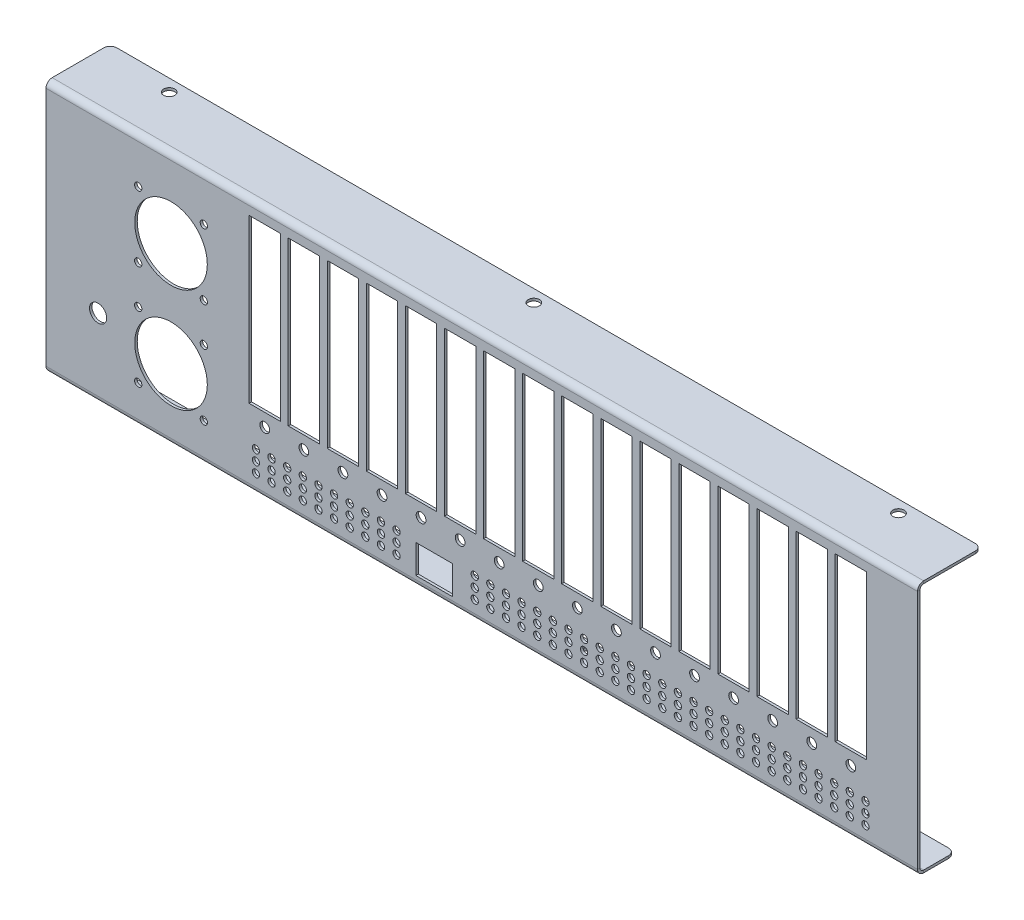
SolidWorks part; units mm, degrees
note: The reader was unsure of these and kept them because the rebuilt part matched: thickness of "Base-Flange", "Edge-Flange1", "Edge-Flange2".
ref_plane "Front" through (0, 0, 0) normal (0, 0, 1) x (1, 0, 0)
ref_plane "Top" through (0, 0, 0) normal (0, 1, 0) x (1, 0, 0)
ref_plane "Right" through (0, 0, 0) normal (1, 0, 0) x (0, 0, -1)
sketch "Sketch1" plane through (0, 0, 0) normal (0, 0, 1) x (1, 0, 0)
  line L1 (0, 0) -> (424.942, 0)
  line L2 (0, 0) -> (0, 123.3424)
  line L3 (0, 123.3424) -> (424.942, 123.3424)
  line L4 (424.942, 0) -> (424.942, 123.3424)
  dimension "Width" = 424.942
  dimension "Back Panel Height" = 123.3424
sheet metal parameters "Sheet-Metal1" thickness 1.2192 parameters "D1"=1.778
base flange "Base-Flange" sketch "Sketch1" thickness 1.2192 parameters "D1"=1.778
edge flange "Edge-Flange1" sketch "Sketch9" bend radius 1.778 thickness 1.2192 parameters "D6"=10
sketch "Sketch9" plane through (0, 123.3424, 0) normal (0, -1, 0) x (-1, 0, 0)
  line L1 (0, 0) -> (-424.942, 0) construction
  line L2 (-424.942, 0) -> (-424.942, 30.1498)
  line L3 (-424.942, 30.1498) -> (0, 30.1498)
  line L4 (0, 30.1498) -> (0, 0)
  line L5 (0, 0) -> (-424.942, 0)
bend "EdgeBend1" bend radius 1.778 bend angle 90 parameters "D5"=1
edge flange "Edge-Flange2" sketch "Sketch12" bend radius 1.778 thickness 1.2192 parameters "D6"=10
sketch "Sketch12" plane through (0, 0, 0) normal (0, 1, 0) x (1, 0, 0)
  line L1 (424.942, 0) -> (0, 0) construction
  line L2 (0, 0) -> (0, 17.145)
  line L3 (0, 17.145) -> (424.942, 17.145)
  line L4 (424.942, 17.145) -> (424.942, 0)
  line L5 (424.942, 0) -> (0, 0)
bend "EdgeBend2" bend radius 1.778 bend angle 90 parameters "D5"=2
sketch "Sketch13" plane through (0, 0, 0) normal (0, -1, 0) x (1, 0, 0)
  line L0 (0, 1.2192) -> (424.942, 1.2192) construction
  line L1 (250.571, -17.145) -> (250.571, 16.8625) construction
  circle A0 centre (34.671, -11.4808) radius 2.4765
  circle A1 centre (250.571, -11.4808) radius 2.4765
  circle A2 centre (390.271, -11.4808) radius 2.4765
  dimension "D1" = 4.953
  dimension "D2" = 12.7
  dimension "D3" = 215.9
  dimension "D4" = 139.7
extrude "8-32 Clearance For Chassi Studs" cut sketch "Sketch13" against normal blind 1.2192
sketch "Sketch14" plane through (0, 123.3424, 0) normal (0, 1, 0) x (-1, 0, 0)
  line L1 (-212.471, -1.778) -> (-212.471, -47.511) construction
  line L2 (-424.942, 1.2192) -> (0, 1.2192) construction
  line L4 (0, -1.778) -> (-424.942, -1.778) construction
  circle A0 centre (-390.271, -24.1808) radius 2.7051
  circle A1 centre (-212.471, -24.1808) radius 2.7051
  circle A2 centre (-34.671, -24.1808) radius 2.7051
  dimension "D1" = 5.4102
  dimension "D4" = 177.8
  dimension "D3" = 25.4
extrude "8-32 PEM Nuts For Cover Attachment" cut sketch "Sketch14" against normal blind 1.2192
fillet "Fillet1" radius 3.175 4 edges at (0, 122.7328, -30.1498) (424.942, 122.7328, -30.1498) (424.942, 0.6096, -17.145) (0, 0.6096, -17.145)
sketch "Sketch16" plane through (0, 0, 1.2192) normal (0, 0, 1) x (1, 0, 0)
  line L0 (424.942, 2.9972) -> (424.942, 120.3452) construction
  line L2 (424.942, 0) -> (0, 0) construction
  line L3 (384.81, 116.205) -> (400.05, 116.205)
  line L4 (384.81, 116.205) -> (384.81, 36.83)
  line L5 (384.81, 36.83) -> (400.05, 36.83)
  line L6 (400.05, 116.205) -> (400.05, 36.83)
  circle A0 centre (392.43, 30.48) radius 2.3813
  dimension "D1" = 4.7625
  dimension "D2" = 32.512
  dimension "D4" = 79.375
  dimension "D3" = 6.35
  dimension "D5" = 15.24
  dimension "D6" = 7.62
  dimension "D7" = 30.48
extrude "Cut-Extrude5" cut sketch "Sketch16" against normal blind 12.54
pattern_linear "LPattern1" count 16 spacing 19.05 along (-1, 0, 0) of "Cut-Extrude5"
sketch "Sketch17" plane through (0, 0, 1.2192) normal (0, 0, 1) x (1, 0, 0)
  line L0 (0, 120.3452) -> (0, 2.9972) construction
  line L1 (180.34, 18.7452) -> (198.12, 18.7452)
  line L2 (180.34, 18.7452) -> (180.34, 4.7752)
  line L3 (180.34, 4.7752) -> (198.12, 4.7752)
  line L4 (198.12, 18.7452) -> (198.12, 4.7752)
  line L5 (424.942, 1.2192) -> (0, 1.2192) construction
  dimension "D1" = 180.34
  dimension "D2" = 3.556
  dimension "D3" = 17.78
  dimension "D4" = 13.97
extrude "NIC port" cut sketch "Sketch17" against normal blind 2.54
sketch "air holes" plane through (0, 0, 1.2192) normal (0, 0, 1) x (1, 0, 0)
  line L0 (424.942, 0) -> (0, 0) construction
  line L1 (424.942, 2.9972) -> (424.942, 120.3452) construction
  circle A1 centre (399.542, 8.89) radius 1.778
  dimension "D1" = 3.556
  dimension "D2" = 8.89
  dimension "D3" = 25.4
extrude "Cut-Extrude7" cut sketch "air holes" against normal blind 2.54
pattern_linear "air hole pattern" count 3 spacing 5.08 along (0, 1, 0) count 40 spacing 7.62 along (-1, 0, 0) skipping (0, 26), (0, 27), (0, 28), (0, 29), (1, 26), (1, 27), (1, 28), (1, 29), (2, 26), (2, 27), (2, 28), (2, 29) of "Cut-Extrude7"
sketch "fan mount holes" plane through (0, 0, 1.2192) normal (0, 0, 1) x (1, 0, 0)
  line L0 (424.942, 120.3452) -> (0, 120.3452) construction
  line L1 (0, 120.3452) -> (0, 2.9972) construction
  circle A0 centre (60.96, 85.2952) radius 17.6941
  circle A1 centre (76.96, 101.2952) radius 1.778
  circle A2 centre (76.96, 69.2952) radius 1.778
  circle A3 centre (44.96, 69.2952) radius 1.778
  circle A4 centre (44.96, 101.2952) radius 1.778
  point P0 (60.96, 85.2952)
  dimension "D1" = 16
  dimension "D2" = 3.556
  dimension "D3" = 3.556
  dimension "D4" = 3.556
  dimension "D5" = 3.556
  dimension "D6" = 16
  dimension "D7" = 16
  dimension "D8" = 16
  dimension "D9" = 19.05
  dimension "D10" = 60.96
extrude "Cut-Extrude9" cut sketch "fan mount holes" against normal blind 2.54
pattern_linear "LPattern2" count 2 spacing 50.8 along (0, -1, 0) of "Cut-Extrude9"
ref_plane "Plane1" through (19.845, 6.096, -200.2078) normal (0, -1, 0) x (1, 0, 0)
sketch "Sketch18" plane through (0, 0, 1.2192) normal (0, 0, 1) x (1, 0, 0)
  line L0 (424.942, 0) -> (0, 0) construction
  line L1 (0, 120.3452) -> (0, 2.9972) construction
  circle A0 centre (25.4, 38.1) radius 4.191
  dimension "D1" = 8.382
  dimension "D2" = 38.1
  dimension "D3" = 25.4
extrude "Hole for Power Jack" cut sketch "Sketch18" against normal blind 2.54
flat pattern "Flat-Pattern1"
sketch "Bend-Lines1" plane through (0, 0, 1.2192) normal (0, 0, 1) x (1, 0, 0)
  line L0 (424.942, 1.3614) -> (0, 1.3614) construction
  line L1 (0, 165.5166) -> (424.942, 165.5166) construction
bend of the flat pattern "Flatten-<EdgeBend1>1"
bend of the flat pattern "Flatten-<EdgeBend2>1"
